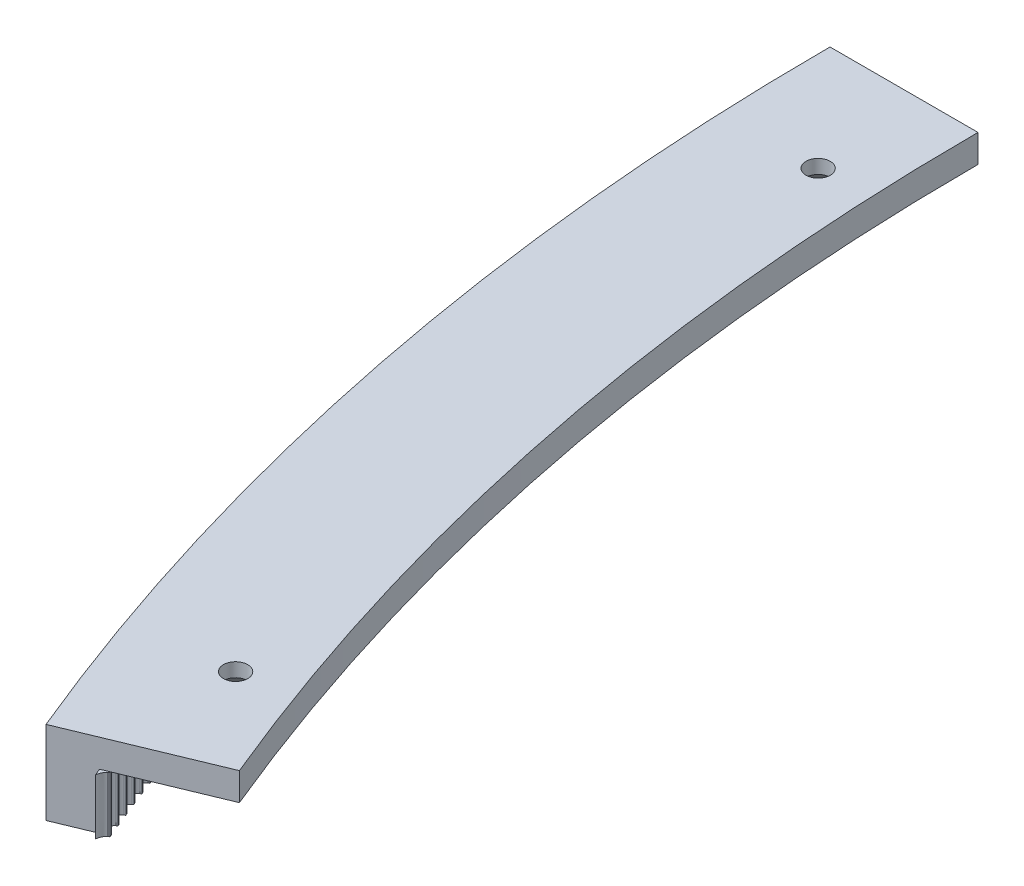
SolidWorks part; units mm, degrees
ref_plane "Front Plane" through (0, 0, 0) normal (0, 0, 1) x (1, 0, 0)
ref_plane "Top Plane" through (0, 0, 0) normal (0, 1, 0) x (1, 0, 0)
ref_plane "Right Plane" through (0, 0, 0) normal (1, 0, 0) x (0, 0, -1)
sketch "Sketch3" plane through (0, 0, 0) normal (0, 0, 1) x (1, 0, 0)
  line L0 (-413.4589, -4.7625) -> (-438.8589, -4.7625)
  line L4 (-424.8889, -9.525) -> (-413.4589, -9.525)
  line L5 (-413.4589, -9.525) -> (-413.4589, -4.7625)
  line L6 (-424.8889, -9.525) -> (-431.2389, -9.525)
  line L8 (-431.2389, -9.525) -> (-431.2389, -19.05)
  line L10 (-438.8589, -19.05) -> (-431.2389, -19.05)
  line L12 (-438.8589, -19.05) -> (-438.8589, -4.7625)
  dimension "D1" = 7.62
  dimension "D3" = 17.78
  dimension "D4" = 4.7625
sketch "Sketch5" plane through (0, 0, 0) normal (0, 0, 1) x (1, 0, 0)
  line L0 (0, 0) -> (0, 189.1302) construction
revolve "Revolve1" add sketch "Sketch3" angle 22.5 about L0
sketch "Sketch7" plane through (0, -9.525, 0) normal (0, -1, 0) x (1, 0, 0)
  line L0 (-431.2389, 0) -> (-413.4589, 0) construction
  line L1 (-398.4128, 165.028) -> (-381.9863, 158.2239) construction
  circle A0 centre (-421.8451, 19.05) radius 2.0828
  arc A1 (-381.9863, 158.2239) -> (-413.4589, 0) centre (0, 0) ccw construction
  circle A5 centre (-397.0242, 143.8332) radius 2.0828
  dimension "D1" = 19.05
  dimension "D3" = 422.275
  dimension "D2" = 422.275
  dimension "D4" = 19.05
extrude "Cut-Extrude1" cut sketch "Sketch7" against normal through all
sketch "Sketch10" plane through (0, -9.525, 0) normal (0, -1, 0) x (1, 0, 0)
  line L0 (-430.6199, -0.2319) -> (-430.3634, -0.2184)
  line L1 (-430.608, 0.2223) -> (-430.3526, 0.1954)
  arc A0 (-430.3526, 0.1954) -> (-430.3634, -0.2184) centre (-426.8927, -0.1022) ccw
  arc A2 (-431.8218, 1.3014) -> (-431.8227, -1.1394) centre (-215.9, 0) ccw
  spline S0 degree 3 poles (-431.8227, -1.1394) (-431.5179, -0.6655) (-431.1171, -0.3631) (-430.6199, -0.2319) knots 0.132959 0.132959 0.132959 0.132959 1 1 1 1
  spline S1 degree 3 poles (-431.8218, 1.3014) (-431.5382, 0.7505) (-431.1334, 0.3908) (-430.608, 0.2223) knots 0.069618 0.069618 0.069618 0.069618 1 1 1 1
extrude "Boss-Extrude1" add sketch "Sketch10" along normal blind 9.525
pattern_circular "CirPattern1" count 70 over 22.5 about axis through (0, -9.525, 0) along (0, -1, 0) of "Boss-Extrude1" reverse direction yes
chamfer "Chamfer1" distance 2.38 angle 45 2 edges at (-421.8451, -9.525, 16.9672) (-397.0242, -9.525, 141.7504)
